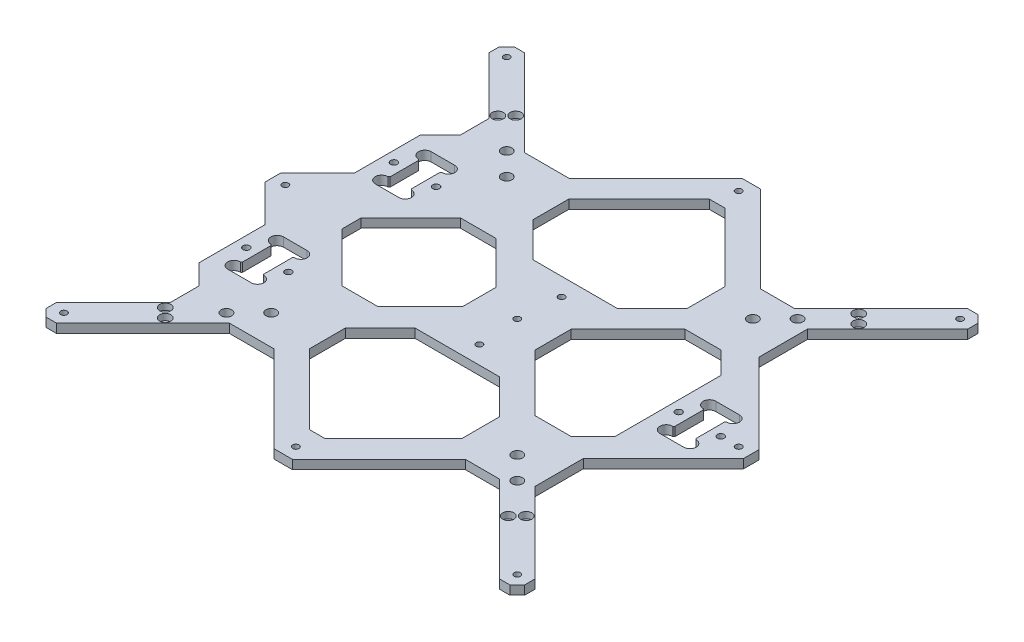
SolidWorks part; units mm, degrees
material "6063-O, Extruded Rod (SS)"
ref_plane "Front Plane" through (0, 0, 0) normal (0, 0, 1) x (1, 0, 0)
ref_plane "Top Plane" through (0, 0, 0) normal (0, 1, 0) x (1, 0, 0)
ref_plane "Right Plane" through (0, 0, 0) normal (1, 0, 0) x (0, 0, -1)
sketch "Sketch2" plane through (0, 0, 0) normal (0, 1, 0) x (1, 0, 0)
  line L0 (162, 177.023) -> (141.977, 157)
  line L1 (141.977, 157) -> (125, 157)
  line L2 (125, 157) -> (101.5, 180.5)
  line L3 (101.5, 189.5) -> (125, 213)
  line L4 (125, 213) -> (141.977, 213)
  line L5 (141.977, 213) -> (162, 192.977)
  line L6 (251.5, 210.0147) -> (240.9853, 220.5294)
  line L7 (240.9853, 220.5294) -> (224.0147, 220.5294)
  line L8 (224.0147, 220.5294) -> (197, 193.5147)
  line L9 (197, 176.4853) -> (224.0147, 149.4706)
  line L10 (224.0147, 149.4706) -> (240.9853, 149.4706)
  line L11 (240.9853, 149.4706) -> (251.5, 159.9853)
  line L12 (184.4001, 296) -> (225.4001, 255)
  line L13 (225.4001, 255) -> (241.5147, 255)
  line L14 (241.5147, 255) -> (282.5147, 296)
  line L15 (282.5147, 296) -> (287.4852, 296)
  line L16 (287.4852, 296) -> (291, 292.4852)
  line L17 (291, 292.4852) -> (291, 287.5147)
  line L18 (291, 287.5147) -> (253, 249.5147)
  line L19 (253, 249.5147) -> (253, 226.667)
  line L20 (253, 226.667) -> (291, 188.667)
  line L21 (291, 188.667) -> (291, 181.333)
  line L22 (291, 181.333) -> (253, 143.333)
  line L23 (253, 143.333) -> (253, 120.4853)
  line L24 (253, 120.4853) -> (291, 82.4853)
  line L25 (291, 82.4853) -> (291, 77.5148)
  line L26 (291, 77.5148) -> (287.4852, 74)
  line L27 (287.4852, 74) -> (282.5147, 74)
  line L28 (282.5147, 74) -> (241.5147, 115)
  line L29 (241.5147, 115) -> (225.4001, 115)
  line L30 (225.4001, 115) -> (184.4001, 74)
  line L31 (184.4001, 74) -> (175.5999, 74)
  line L32 (175.5999, 74) -> (134.5999, 115)
  line L33 (134.5999, 115) -> (113.4853, 115)
  line L34 (113.4853, 115) -> (72.4853, 74)
  line L35 (72.4853, 74) -> (67.5148, 74)
  line L36 (67.5148, 74) -> (64, 77.5148)
  line L37 (64, 77.5148) -> (64, 82.4853)
  line L38 (64, 82.4853) -> (91, 109.4853)
  line L39 (91, 109.4853) -> (91, 123)
  line L40 (91, 123) -> (81.5, 132.5)
  line L41 (81.5, 132.5) -> (81.5, 163.7609)
  line L42 (81.5, 163.7609) -> (64, 181.2609)
  line L43 (64, 188.7391) -> (81.5, 206.2391)
  line L44 (81.5, 206.2391) -> (81.5, 237.5)
  line L45 (81.5, 237.5) -> (91, 247)
  line L46 (91, 247) -> (91, 260.5147)
  line L47 (91, 260.5147) -> (64, 287.5147)
  line L48 (64, 287.5147) -> (64, 292.4852)
  line L49 (64, 292.4852) -> (67.5148, 296)
  line L50 (67.5148, 296) -> (72.4853, 296)
  line L51 (72.4853, 296) -> (113.4853, 255)
  line L52 (113.4853, 255) -> (134.5999, 255)
  line L53 (134.5999, 255) -> (175.5999, 296)
  line L54 (175.5999, 296) -> (184.4001, 296)
  line L55 (143, 246.4158) -> (143, 229.5663)
  line L56 (143, 229.5663) -> (159.5663, 213)
  line L57 (159.5663, 213) -> (199.5147, 213)
  line L58 (199.5147, 213) -> (216, 229.4853)
  line L59 (216, 229.4853) -> (216, 247.4296)
  line L60 (216, 247.4296) -> (183.6826, 279.747)
  line L61 (183.6826, 279.747) -> (176.3174, 279.7332)
  line L62 (176.3174, 279.7332) -> (143, 246.4158)
  line L63 (143, 123.5842) -> (143, 140.4337)
  line L64 (143, 140.4337) -> (159.5663, 157)
  line L65 (159.5663, 157) -> (199.5147, 157)
  line L66 (199.5147, 157) -> (216, 140.5147)
  line L67 (216, 140.5147) -> (216, 122.5704)
  line L68 (216, 122.5704) -> (183.6826, 90.253)
  line L69 (183.6826, 90.253) -> (176.3174, 90.2668)
  line L70 (176.3174, 90.2668) -> (143, 123.5842)
  line L71 (101.5, 226.75) -> (101.5, 213.25)
  line L72 (271.5, 191.75) -> (271.5, 178.25)
  line L73 (101.5, 156.75) -> (101.5, 143.25)
  line L74 (91.5, 226.75) -> (91.5, 213.25)
  line L75 (261.5, 191.75) -> (261.5, 178.25)
  line L76 (91.5, 156.75) -> (91.5, 143.25)
  line L77 (93.6792, 358.4107) -> (93.6792, 347.8262)
  line L78 (93.6792, 347.8262) -> (93.9406, 345.7354)
  line L79 (93.9406, 345.7354) -> (94.4633, 344.2327)
  line L80 (94.4633, 344.2327) -> (95.182, 343.1873)
  line L81 (95.182, 343.1873) -> (96.1846, 341.9648)
  line L82 (96.1846, 341.9648) -> (97.8105, 341.4329)
  line L83 (97.8105, 341.4329) -> (99.6248, 341.0966)
  line L84 (99.6248, 341.0966) -> (101.977, 341.3579)
  line L85 (101.977, 341.3579) -> (104.0024, 342.4033)
  line L86 (104.0024, 342.4033) -> (105.1131, 344.2327)
  line L87 (105.1131, 344.2327) -> (105.5705, 346.7155)
  line L88 (105.5705, 346.7155) -> (105.5705, 349.1983)
  line L89 (105.5705, 349.1983) -> (105.5705, 358.4107)
  line L90 (79.8932, 349.3289) -> (80.0892, 349.3289)
  line L91 (80.0892, 349.3289) -> (81.0039, 348.8063)
  line L92 (81.0039, 348.8063) -> (82.0493, 347.4342)
  line L93 (82.0493, 347.4342) -> (86.4922, 341.0966)
  line L94 (73.5556, 341.1619) -> (73.5556, 358.4107)
  line L95 (73.5556, 358.4107) -> (80.6119, 358.4107)
  line L96 (80.6119, 358.4107) -> (82.768, 357.7574)
  line L97 (82.768, 357.7574) -> (83.8134, 356.7773)
  line L98 (83.8134, 356.7773) -> (84.5321, 355.4706)
  line L99 (84.5321, 355.4706) -> (84.8588, 353.7065)
  line L100 (84.8588, 353.7065) -> (84.5321, 352.0078)
  line L101 (84.5321, 352.0078) -> (83.6827, 350.5703)
  line L102 (83.6827, 350.5703) -> (82.5067, 349.8517)
  line L103 (82.5067, 349.8517) -> (81.3306, 349.525)
  line L104 (81.3306, 349.525) -> (79.8932, 349.3289)
  line L105 (79.8932, 349.3289) -> (78.1291, 349.3289)
  line L106 (78.1291, 349.3289) -> (73.5556, 349.3289)
  line L107 (113.0897, 345.4442) -> (114.2004, 343.4842)
  line L108 (114.2004, 343.4842) -> (116.6178, 341.8507)
  line L109 (116.6178, 341.8507) -> (118.9699, 341.1974)
  line L110 (118.9699, 341.1974) -> (122.4328, 341.7201)
  line L111 (122.4328, 341.7201) -> (124.0662, 343.0268)
  line L112 (124.0662, 343.0268) -> (125.2422, 345.1176)
  line L113 (125.2422, 345.1176) -> (125.2422, 346.359)
  line L114 (125.2422, 346.359) -> (124.9156, 347.4697)
  line L115 (124.9156, 347.4697) -> (123.7395, 348.7764)
  line L116 (123.7395, 348.7764) -> (122.5635, 349.2991)
  line L117 (122.5635, 349.2991) -> (116.7485, 351.0632)
  line L118 (116.7485, 351.0632) -> (115.0497, 352.1739)
  line L119 (115.0497, 352.1739) -> (114.0044, 353.4153)
  line L120 (114.0044, 353.4153) -> (113.8737, 354.5914)
  line L121 (113.8737, 354.5914) -> (114.135, 356.3554)
  line L122 (114.135, 356.3554) -> (115.3764, 357.6622)
  line L123 (115.3764, 357.6622) -> (117.4672, 358.4462)
  line L124 (117.4672, 358.4462) -> (120.0807, 358.5769)
  line L125 (120.0807, 358.5769) -> (122.8248, 357.8582)
  line L126 (122.8248, 357.8582) -> (123.9355, 356.8128)
  line L127 (123.9355, 356.8128) -> (124.3929, 355.5714)
  line L128 (130.9954, 341.0312) -> (137.9864, 358.5414)
  line L129 (137.9864, 358.5414) -> (139.0972, 358.5414)
  line L130 (139.0972, 358.5414) -> (145.9575, 341.0312)
  line L131 (143.9343, 346.1951) -> (133.0803, 346.1927)
  line L132 (55, 341.1619) -> (55, 358.4107)
  line L133 (55, 358.4107) -> (62.0563, 358.4107)
  line L134 (62.0563, 358.4107) -> (64.2125, 357.7574)
  line L135 (64.2125, 357.7574) -> (65.2578, 356.7773)
  line L136 (65.2578, 356.7773) -> (65.9765, 355.4706)
  line L137 (65.9765, 355.4706) -> (66.3032, 353.7065)
  line L138 (66.3032, 353.7065) -> (65.9765, 352.0078)
  line L139 (65.9765, 352.0078) -> (65.1272, 350.5703)
  line L140 (65.1272, 350.5703) -> (63.9511, 349.8517)
  line L141 (63.9511, 349.8517) -> (62.7751, 349.525)
  line L142 (62.7751, 349.525) -> (61.3376, 349.3289)
  line L143 (61.3376, 349.3289) -> (59.5735, 349.3289)
  line L144 (59.5735, 349.3289) -> (55, 349.3289)
  line L145 (251.5, 210.0147) -> (251.5, 159.9853)
  line L146 (197, 193.5147) -> (197, 176.4853)
  line L147 (64, 188.7391) -> (64, 181.2609)
  line L148 (101.5, 189.5) -> (101.5, 180.5)
  line L149 (162, 192.977) -> (162, 177.023)
  line L150 (102.1, 142.75) -> (102, 142.75)
  line L151 (272.1, 177.75) -> (272, 177.75)
  line L152 (102.1, 212.75) -> (102, 212.75)
  line L153 (90.9, 142.75) -> (91, 142.75)
  line L154 (260.9, 177.75) -> (261, 177.75)
  line L155 (90.9, 212.75) -> (91, 212.75)
  line L156 (102, 142.75) -> (101.5, 143.25)
  line L157 (272, 177.75) -> (271.5, 178.25)
  line L158 (102, 212.75) -> (101.5, 213.25)
  line L159 (91, 142.75) -> (91.5, 143.25)
  line L160 (261, 177.75) -> (261.5, 178.25)
  line L161 (91, 212.75) -> (91.5, 213.25)
  line L162 (102.1, 157.25) -> (102, 157.25)
  line L163 (272.1, 192.25) -> (272, 192.25)
  line L164 (102.1, 227.25) -> (102, 227.25)
  line L165 (90.9, 157.25) -> (91, 157.25)
  line L166 (260.9, 192.25) -> (261, 192.25)
  line L167 (90.9, 227.25) -> (91, 227.25)
  line L168 (101.5, 156.75) -> (102, 157.25)
  line L169 (271.5, 191.75) -> (272, 192.25)
  line L170 (101.5, 226.75) -> (102, 227.25)
  line L171 (91.5, 156.75) -> (91, 157.25)
  line L172 (261.5, 191.75) -> (261, 192.25)
  line L173 (91.5, 226.75) -> (91, 227.25)
  line L174 (90.9, 163.25) -> (102.1, 163.25)
  line L175 (260.9, 198.25) -> (272.1, 198.25)
  line L176 (90.9, 233.25) -> (102.1, 233.25)
  line L177 (90.9, 136.75) -> (102.1, 136.75)
  line L178 (260.9, 171.75) -> (272.1, 171.75)
  line L179 (90.9, 206.75) -> (102.1, 206.75)
  arc A0 (102.1, 206.75) -> (102.1, 212.75) centre (102.1, 209.75) ccw
  arc A1 (272.1, 171.75) -> (272.1, 177.75) centre (272.1, 174.75) ccw
  arc A2 (102.1, 136.75) -> (102.1, 142.75) centre (102.1, 139.75) ccw
  arc A3 (90.9, 142.75) -> (90.9, 136.75) centre (90.9, 139.75) ccw
  arc A4 (90.9, 212.75) -> (90.9, 206.75) centre (90.9, 209.75) ccw
  arc A5 (260.9, 177.75) -> (260.9, 171.75) centre (260.9, 174.75) ccw
  arc A6 (102.1, 157.25) -> (102.1, 163.25) centre (102.1, 160.25) ccw
  arc A7 (102.1, 227.25) -> (102.1, 233.25) centre (102.1, 230.25) ccw
  arc A8 (272.1, 192.25) -> (272.1, 198.25) centre (272.1, 195.25) ccw
  arc A9 (90.9, 163.25) -> (90.9, 157.25) centre (90.9, 160.25) ccw
  arc A10 (260.9, 198.25) -> (260.9, 192.25) centre (260.9, 195.25) ccw
  arc A11 (90.9, 233.25) -> (90.9, 227.25) centre (90.9, 230.25) ccw
  circle A12 centre (318.6, 4.9) radius 2.55
  circle A13 centre (318.6, 28.1) radius 2.55
  circle A14 centre (295.4, 28.1) radius 2.55
  circle A15 centre (295.4, 4.9) radius 2.55
  circle A16 centre (281.6, 4.9) radius 2.55
  circle A17 centre (258.4, 4.9) radius 2.55
  circle A18 centre (258.4, 28.1) radius 2.55
  circle A19 centre (281.6, 28.1) radius 2.55
  circle A20 centre (111.6, 4.9) radius 2.55
  circle A21 centre (111.6, 28.1) radius 2.55
  circle A22 centre (88.4, 28.1) radius 2.55
  circle A23 centre (88.4, 4.9) radius 2.55
  circle A24 centre (74.6, 4.9) radius 2.55
  circle A25 centre (74.6, 28.1) radius 2.55
  circle A26 centre (51.4, 28.1) radius 2.55
  circle A27 centre (51.4, 4.9) radius 2.55
  circle A28 centre (360, 39.8) radius 1.5
  circle A29 centre (10, 39.8) radius 1.5
  circle A30 centre (340, 359.8) radius 1.5
  circle A31 centre (30, 39.8) radius 1.5
  circle A32 centre (42.9, 67.8) radius 1.5
  circle A33 centre (340, 39.8) radius 1.5
  circle A34 centre (10, 359.8) radius 1.5
  circle A35 centre (350, 19.8) radius 1.5
  circle A36 centre (47, 99.8) radius 1.5
  circle A37 centre (3.7, 181.1) radius 1.5
  circle A38 centre (20, 19.8) radius 1.5
  circle A39 centre (4.9, 67.8) radius 1.5
  circle A40 centre (360, 359.8) radius 1.5
  circle A41 centre (42.9, 161.8) radius 1.5
  circle A42 centre (3.7, 99.8) radius 1.5
  circle A43 centre (30, 359.8) radius 1.5
  circle A44 centre (47, 174.7) radius 1.5
  circle A45 centre (4.9, 161.8) radius 1.5
  circle A46 centre (46.5, 269.3) radius 1.5
  circle A47 centre (15, 247.8) radius 1.5
  circle A48 centre (3.5, 269.3) radius 1.5
  circle A49 centre (15, 290.8) radius 1.5
  circle A50 centre (180, 80) radius 1.5
  circle A51 centre (180, 290) radius 1.5
  circle A52 centre (285, 80) radius 1.5
  circle A53 centre (70, 290) radius 1.5
  circle A54 centre (285, 290) radius 1.5
  circle A55 centre (70, 185) radius 1.5
  circle A56 centre (180, 185) radius 1.5
  circle A57 centre (285, 185) radius 1.5
  circle A58 centre (256.5, 185) radius 1.6
  circle A59 centre (276.5, 185) radius 1.6
  circle A60 centre (106.5, 220) radius 1.6
  circle A61 centre (106.5, 150) radius 1.6
  circle A62 centre (86.5, 220) radius 1.6
  circle A63 centre (86.5, 150) radius 1.6
  circle A64 centre (70, 80) radius 1.5
  circle A65 centre (181.5, 165.5) radius 1.5
  circle A66 centre (181.5, 204.5) radius 1.5
  circle A67 centre (40, 7) radius 1.6
  circle A68 centre (331, 7) radius 1.6
  circle A69 centre (343, 7) radius 1.6
  circle A70 centre (120, 13) radius 1.6
  circle A71 centre (120, 4) radius 1.6
  circle A72 centre (230, 13) radius 1.6
  circle A73 centre (230, 4) radius 1.6
  circle A74 centre (333.4, 205) radius 2.1
  circle A75 centre (333.4, 88) radius 2.1
  circle A76 centre (26, 7) radius 1.6
  circle A77 centre (153, 13) radius 1.6
  circle A78 centre (153, 4) radius 1.6
  spline S0 degree 2 poles (5, 370) (2.5, 367.5) (0, 365) knots 1472.868668 1472.868668 1472.868668 1479.939736 1479.939736 1479.939736
  spline S1 degree 2 poles (365, 370) (185, 370) (5, 370) knots 1112.868668 1112.868668 1112.868668 1472.868668 1472.868668 1472.868668
  spline S2 degree 2 poles (370, 365) (367.5, 367.5) (365, 370) knots 1105.7976 1105.7976 1105.7976 1112.868668 1112.868668 1112.868668
  spline S3 degree 2 poles (370, 5) (370, 185) (370, 365) knots 745.7976 745.7976 745.7976 1105.7976 1105.7976 1105.7976
  spline S4 degree 2 poles (365, 0) (367.5, 2.5) (370, 5) knots 738.726533 738.726533 738.726533 745.7976 745.7976 745.7976
  spline S5 degree 2 poles (345, 0) (355, 0) (365, 0) knots 718.726533 718.726533 718.726533 738.726533 738.726533 738.726533
  spline S6 degree 2 poles (341, 4) (343, 2) (345, 0) knots 710.241251 710.241251 710.241251 718.726533 718.726533 718.726533
  spline S7 degree 2 poles (333, 4) (337, 4) (341, 4) knots 704.241251 704.241251 704.241251 710.241251 710.241251 710.241251
  spline S8 degree 2 poles (329, 0) (331, 2) (333, 4) knots 698.584397 698.584397 698.584397 704.241251 704.241251 704.241251
  spline S9 degree 2 poles (151, 0) (240, 0) (329, 0) knots 507.584397 507.584397 507.584397 698.584397 698.584397 698.584397
  spline S10 degree 2 poles (146, 5) (148.5, 2.5) (151, 0) knots 501.927543 501.927543 501.927543 507.584397 507.584397 507.584397
  spline S11 degree 2 poles (127, 5) (136.5, 5) (146, 5) knots 487.927543 487.927543 487.927543 501.927543 501.927543 501.927543
  spline S12 degree 2 poles (122, 0) (124.5, 2.5) (127, 5) knots 482.270688 482.270688 482.270688 487.927543 487.927543 487.927543
  spline S13 degree 2 poles (41, 0) (81.5, 0) (122, 0) knots 407.270688 407.270688 407.270688 482.270688 482.270688 482.270688
  spline S14 degree 2 poles (37, 4) (39, 2) (41, 0) knots 401.613834 401.613834 401.613834 407.270688 407.270688 407.270688
  spline S15 degree 2 poles (29, 4) (33, 4) (37, 4) knots 395.613834 395.613834 395.613834 401.613834 401.613834 401.613834
  spline S16 degree 2 poles (25, 0) (27, 2) (29, 4) knots 387.128553 387.128553 387.128553 395.613834 395.613834 395.613834
  spline S17 degree 2 poles (5, 0) (15, 0) (25, 0) knots 367.128553 367.128553 367.128553 387.128553 387.128553 387.128553
  spline S18 degree 2 poles (0, 5) (2.5, 2.5) (5, 0) knots 360.191742 360.191742 360.191742 367.128553 367.128553 367.128553
  spline S19 degree 2 poles (0, 365) (0, 185) (0, 5) knots 0 0 0 360.191742 360.191742 360.191742
  spline S20 degree 2 poles (93, 31.5) (100, 31.5) (107, 31.5) knots 1110.421356 1110.421356 1110.421356 1117.046356 1117.046356 1117.046356
  spline S21 degree 2 poles (88, 36.5) (90.5, 34) (93, 31.5) knots 1103.350288 1103.350288 1103.350288 1110.421356 1110.421356 1110.421356
  spline S22 degree 2 poles (83, 36.5) (85.5, 36.5) (88, 36.5) knots 1098.350288 1098.350288 1098.350288 1103.350288 1103.350288 1103.350288
  spline S23 degree 2 poles (73, 46.5) (78, 41.5) (83, 36.5) knots 1084.208153 1084.208153 1084.208153 1098.350288 1098.350288 1098.350288
  spline S24 degree 2 poles (55, 46.5) (64, 46.5) (73, 46.5) knots 1066.208153 1066.208153 1066.208153 1084.208153 1084.208153 1084.208153
  spline S25 degree 2 poles (50, 51.5) (52.5, 49) (55, 46.5) knots 1059.137085 1059.137085 1059.137085 1066.208153 1066.208153 1066.208153
  spline S26 degree 2 poles (50, 325) (50, 188.25) (50, 51.5) knots 787.637085 787.637085 787.637085 1059.137085 1059.137085 1059.137085
  spline S27 degree 2 poles (55, 330) (52.5, 327.5) (50, 325) knots 780.566017 780.566017 780.566017 787.637085 787.637085 787.637085
  spline S28 degree 2 poles (315, 330) (185, 330) (55, 330) knots 520.566017 520.566017 520.566017 780.566017 780.566017 780.566017
  spline S29 degree 2 poles (320, 325) (317.5, 327.5) (315, 330) knots 513.494949 513.494949 513.494949 520.566017 520.566017 520.566017
  spline S30 degree 2 poles (320, 51.5) (320, 188.25) (320, 325) knots 241.994949 241.994949 241.994949 513.494949 513.494949 513.494949
  spline S31 degree 2 poles (315, 46.5) (317.5, 49) (320, 51.5) knots 234.923882 234.923882 234.923882 241.994949 241.994949 241.994949
  spline S32 degree 2 poles (297, 46.5) (306, 46.5) (315, 46.5) knots 216.923882 216.923882 216.923882 234.923882 234.923882 234.923882
  spline S33 degree 2 poles (287, 36.5) (292, 41.5) (297, 46.5) knots 202.781746 202.781746 202.781746 216.923882 216.923882 216.923882
  spline S34 degree 2 poles (282, 36.5) (284.5, 36.5) (287, 36.5) knots 197.781746 197.781746 197.781746 202.781746 202.781746 202.781746
  spline S35 degree 2 poles (277, 31.5) (279.5, 34) (282, 36.5) knots 190.710678 190.710678 190.710678 197.781746 197.781746 197.781746
  spline S36 degree 2 poles (263, 31.5) (264, 31.5) (265, 31.5) (270, 31.5) (275, 31.5) (276, 31.5) (277, 31.5) knots 176.710678 176.710678 176.710678 178.710678 178.710678 188.710678 188.710678 190.710678 190.710678 190.710678
  spline S37 degree 2 poles (258, 36.5) (260.5, 34) (263, 31.5) knots 169.63961 169.63961 169.63961 176.710678 176.710678 176.710678
  spline S38 degree 2 poles (210, 36.5) (211.75, 36.5) (213.5, 36.5) (235.75, 36.5) (258, 36.5) knots 121.63961 121.63961 121.63961 125.13961 125.13961 169.63961 169.63961 169.63961
  spline S39 degree 2 poles (190, 16.5) (200, 26.5) (210, 36.5) knots 93.355339 93.355339 93.355339 121.63961 121.63961 121.63961
  spline S40 degree 2 poles (180, 16.5) (185, 16.5) (190, 16.5) knots 83.355339 83.355339 83.355339 93.355339 93.355339 93.355339
  spline S41 degree 2 poles (160, 36.5) (170, 26.5) (180, 16.5) knots 55.071068 55.071068 55.071068 83.355339 83.355339 83.355339
  spline S42 degree 2 poles (112, 36.5) (134.25, 36.5) (156.5, 36.5) (158.25, 36.5) (160, 36.5) knots 7.071068 7.071068 7.071068 51.571068 51.571068 55.071068 55.071068 55.071068
  spline S43 degree 2 poles (107, 31.5) (109.5, 34) (112, 36.5) knots 0 0 0 7.071068 7.071068 7.071068
extrude "Boss-Extrude2" add sketch "Sketch2" along normal blind 4.25 contours L43 L147 L42 L41 L40 L39 L38 L37 L36 L35 L34 L33 L32 L31 L30 L29 L28 L27 L26 L25 L24 L23 L22 L21 L20 L19 L18 L17 L16 L15 L14 L13 L12 L54 L53 L52 L51 L50 L49 L48 L47 L46 L45 L44 A66 A65 A64 region at (170.1997, 0, -185)
sketch "Sketch3" plane through (0, 4.25, 0) normal (0, 1, 0) x (1, 0, 0)
  line L0 (181.5, 203) -> (181.5, 206) construction
  line L1 (180, 204.5) -> (183, 204.5) construction
  line L2 (180, 165.5) -> (183, 165.5) construction
  circle A0 centre (181.5, 204.5) radius 1.5 construction
  circle A1 centre (181.5, 204.5) radius 1.5 construction
  circle A2 centre (181.5, 165.5) radius 1.5 construction
ref_plane "Plane1" through (181.5, 0, 0) normal (1, 0, 0) x (0, 0, -1)
ref_plane "Plane2" through (0, 0, -165.5) normal (0, 0, 1) x (1, 0, 0)
ref_plane "Plane3" through (0, 0, -204.5) normal (0, 0, -1) x (-1, 0, 0)
sketch "Sketch4" plane through (0, 4.25, 0) normal (0, 1, 0) x (1, 0, 0)
  line L0 (91, 260.5147) -> (118.0833, 233.4314) construction
  line L2 (241.5147, 255) -> (228.4314, 241.9167) construction
  line L4 (241.5147, 115) -> (228.4314, 128.0833) construction
  line L7 (113.4853, 115) -> (72.4853, 74) construction
  line L8 (126.5686, 128.0833) -> (118.0833, 136.5686) construction
  line L9 (118.0833, 136.5686) -> (91, 109.4853) construction
  line L10 (64, 82.4853) -> (91, 109.4853) construction
  line L11 (67.5148, 74) -> (64, 77.5148) construction
  line L12 (126.5686, 128.0833) -> (113.4853, 115) construction
  line L13 (122.326, 132.326) -> (65.7574, 75.7574) construction
  line L14 (228.4314, 128.0833) -> (236.9167, 136.5686) construction
  line L15 (236.9167, 136.5686) -> (253, 120.4853) construction
  line L16 (282.5147, 74) -> (241.5147, 115) construction
  line L17 (291, 77.5148) -> (287.4852, 74) construction
  line L18 (118.0833, 233.4314) -> (126.5686, 241.9167) construction
  line L19 (126.5686, 241.9167) -> (113.4853, 255) construction
  line L20 (91, 260.5147) -> (64, 287.5147) construction
  line L21 (64, 292.4852) -> (67.5148, 296) construction
  line L22 (228.4314, 241.9167) -> (236.9167, 233.4314) construction
  line L23 (236.9167, 233.4314) -> (253, 249.5147) construction
  line L24 (291, 287.5147) -> (253, 249.5147) construction
  line L25 (287.4852, 296) -> (291, 292.4852) construction
  line L26 (122.326, 237.674) -> (65.7574, 294.2426) construction
  line L27 (232.674, 237.674) -> (289.2426, 294.2426) construction
  line L28 (232.674, 132.326) -> (289.2426, 75.7574) construction
  circle A4 centre (119.144, 129.144) radius 2.5
  circle A5 centre (108.5374, 118.5374) radius 2.5
  circle A6 centre (108.5374, 251.4626) radius 2.5
  circle A7 centre (119.144, 240.856) radius 2.5
  circle A8 centre (235.856, 240.856) radius 2.5
  circle A9 centre (246.4626, 251.4626) radius 2.5
  circle A10 centre (235.856, 129.144) radius 2.5
  circle A11 centre (246.4626, 118.5374) radius 2.5
  dimension "D4" = 5
  dimension "D7" = 5
  dimension "D8" = 15
  dimension "D10" = 5
  dimension "D11" = 5
  dimension "D14" = 5
  dimension "D15" = 5
  dimension "D18" = 5
  dimension "D19" = 5
  dimension "D2" = 80
  dimension "D3" = 80
  dimension "D5" = 80
  dimension "D6" = 4.5
  dimension "D9" = 80
  dimension "D12" = 15
  dimension "D13" = 4.5
  dimension "D16" = 15
  dimension "D17" = 4.5
  dimension "D20" = 15
  dimension "D21" = 4.5
extrude "Holes-to-drill" cut sketch "Sketch4" against normal through all
sketch "Sketch6" plane through (0, 4.25, 0) normal (0, 1, 0) x (1, 0, 0)
  line L0 (65.7574, 75.7574) -> (94.0417, 104.0417) construction
  line L1 (67.5148, 74) -> (64, 77.5148) construction
  line L2 (91.9204, 106.163) -> (96.163, 101.9204) construction
  line L3 (289.2426, 75.7574) -> (260.9583, 104.0417) construction
  line L4 (291, 77.5148) -> (287.4852, 74) construction
  line L5 (258.837, 101.9204) -> (263.0796, 106.163) construction
  line L6 (65.7574, 294.2426) -> (94.0417, 265.9583) construction
  line L7 (64, 292.4852) -> (67.5148, 296) construction
  line L8 (91.9204, 263.837) -> (96.163, 268.0796) construction
  line L9 (289.2426, 294.2426) -> (260.9583, 265.9583) construction
  line L10 (287.4852, 296) -> (291, 292.4852) construction
  line L11 (258.837, 268.0796) -> (263.0796, 263.837) construction
  circle A0 centre (91.9204, 106.163) radius 1.5
  circle A1 centre (96.163, 101.9204) radius 1.5
  circle A2 centre (258.837, 101.9204) radius 1.5
  circle A3 centre (263.0796, 106.163) radius 1.5
  circle A4 centre (91.9204, 263.837) radius 1.5
  circle A5 centre (96.163, 268.0796) radius 1.5
  circle A6 centre (258.837, 268.0796) radius 1.5
  circle A7 centre (263.0796, 263.837) radius 1.5
  dimension "D2" = 3
  dimension "D3" = 3
  dimension "D6" = 3
  dimension "D7" = 3
  dimension "D9" = 3
  dimension "D10" = 3
  dimension "D12" = 3
  dimension "D13" = 3
  dimension "D1" = 6
  dimension "D4" = 40
  dimension "D5" = 6
  dimension "D8" = 6
  dimension "D11" = 6
extrude "Cut-Extrude1" cut sketch "Sketch6" against normal through all
sketch "Sketch7" plane through (0, 4.25, 0) normal (0, -1, 0) x (1, 0, 0)
  circle A0 centre (91.9204, -106.163) radius 2.65
  circle A1 centre (96.163, -101.9204) radius 2.65
  circle A2 centre (258.837, -101.9204) radius 2.65
  circle A3 centre (263.0796, -106.163) radius 2.65
  circle A4 centre (91.9204, -263.837) radius 2.65
  circle A5 centre (96.163, -268.0796) radius 2.65
  circle A6 centre (258.837, -268.0796) radius 2.65
  circle A7 centre (263.0796, -263.837) radius 2.65
  dimension "D1" = 5.3
  dimension "D2" = 5.3
  dimension "D3" = 5.3
  dimension "D4" = 5.3
  dimension "D5" = 5.3
  dimension "D6" = 5.3
  dimension "D7" = 5.3
  dimension "D8" = 5.3
extrude "Cut-Extrude2" cut sketch "Sketch7" along normal blind 3
